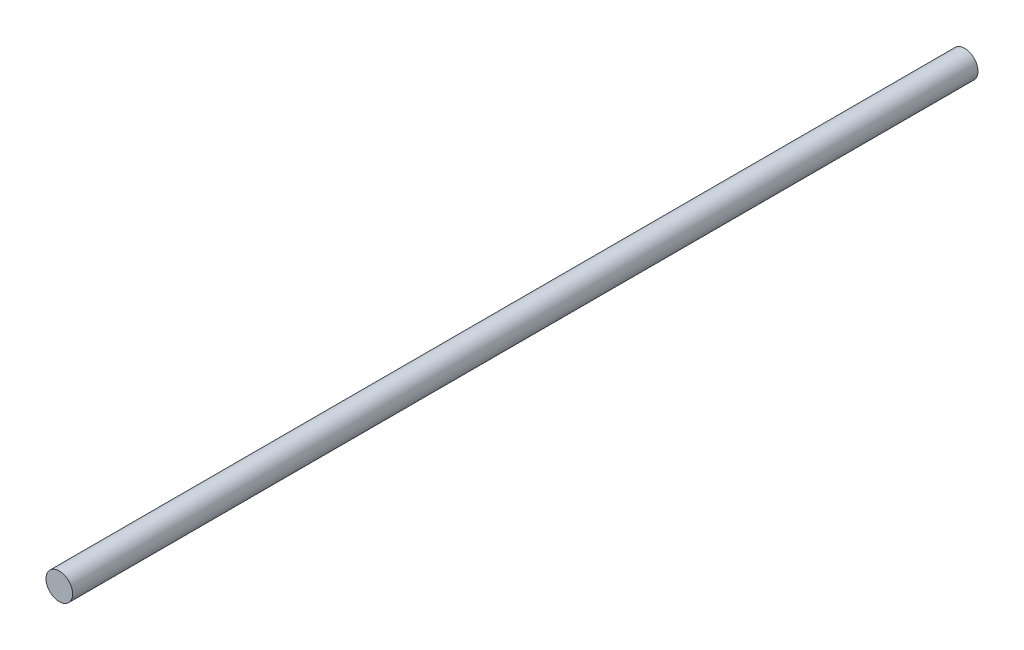
SolidWorks part; units mm, degrees
ref_plane "Front Plane" through (0, 0, 0) normal (0, 0, 1) x (1, 0, 0)
ref_plane "Top Plane" through (0, 0, 0) normal (0, 1, 0) x (1, 0, 0)
ref_plane "Right Plane" through (0, 0, 0) normal (1, 0, 0) x (0, 0, -1)
sketch "Sketch1" plane through (0, 0, 0) normal (0, 0, 1) x (1, 0, 0)
  circle A0 centre (0, 0) radius 5
  dimension "D1" = 10
extrude "Boss-Extrude1" add sketch "Sketch1" along normal blind 340
